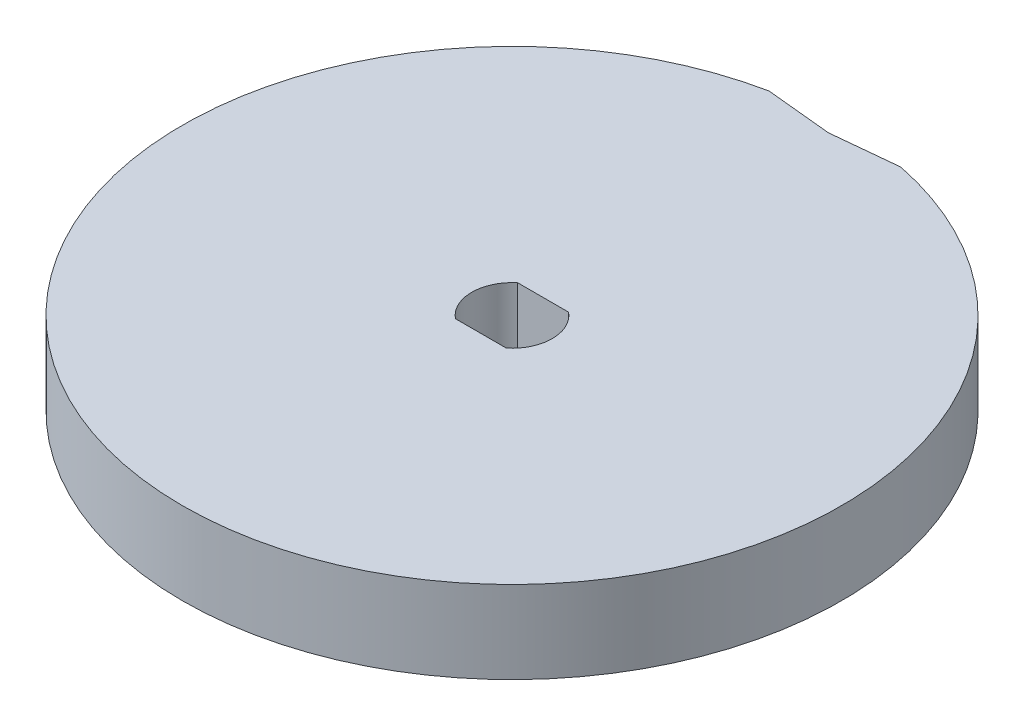
SolidWorks part; units mm, degrees
material "ABS"
ref_plane "Front Plane" through (0, 0, 0) normal (0, 0, 1) x (1, 0, 0)
ref_plane "Top Plane" through (0, 0, 0) normal (0, 1, 0) x (1, 0, 0)
ref_plane "Right Plane" through (0, 0, 0) normal (1, 0, 0) x (0, 0, -1)
ref_axis "x-axis" through (88.99, 0, 0) along (-1, 0, 0)
ref_axis "y-axis" through (0, 0, 55) along (0, 0, -1)
ref_axis "z-axis" through (0, 55, 0) along (0, -1, 0)
sketch "Sketch1" plane through (0, 0, 0) normal (0, 1, 0) x (1, 0, 0)
  circle A0 centre (0, 0) radius 12.7
  dimension "D1" = 25.4
extrude "wheelbase" add sketch "Sketch1" along normal mid plane 3.175
sketch "Sketch3" plane through (0, 1.5875, 0) normal (0, 1, 0) x (1, 0, 0)
  circle A0 centre (0, 0) radius 1.55
  dimension "D1" = 3.1
extrude "circlefit" cut sketch "Sketch3" against normal through all
sketch "Sketch4" plane through (0, 1.5875, 0) normal (0, 1, 0) x (1, 0, 0)
  line L0 (-0.9811, 1.2) -> (0.9811, 1.2)
  circle A0 centre (0, 0) radius 1.55 construction
  arc A1 (-0.9811, 1.2) -> (0.9811, 1.2) centre (0, 0) cw
  dimension "key1" = 1.2
extrude "gm26fit1" add sketch "Sketch4" against normal up to surface (3.175 mm away) up to face at (0, -1.5875, 1.55)
sketch "Sketch5" plane through (0, 1.5875, 0) normal (0, 1, 0) x (1, 0, 0)
  line L0 (-0.9811, -1.2) -> (0.9811, -1.2)
  line L1 (-0.9811, 1.2) -> (0.9811, 1.2) construction
  arc A0 (-0.9811, 1.2) -> (0.9811, 1.2) centre (0, 0) ccw construction
  arc A1 (-0.9811, -1.2) -> (0.9811, -1.2) centre (0, 0) ccw
  dimension "key2" = 2.4
extrude "gm26fit2" add sketch "Sketch5" against normal up to surface (3.175 mm away) up to face at (0, -1.5875, 0.175)
sketch "Sketch6" plane through (0, 1.5875, 0) normal (0, 1, 0) x (1, 0, 0)
  line L0 (-2.54, 12.4434) -> (0, 12.192)
  line L1 (0, 12.192) -> (2.54, 12.4434)
  line L2 (0, 12.192) -> (0, 12.7) construction
  circle A0 centre (0, 0) radius 12.7 construction
  arc A1 (-2.54, 12.4434) -> (2.54, 12.4434) centre (0, 0) cw
  dimension "D1" = 0.508
  dimension "D2" = 5.08
extrude "Cut-Extrude1" cut sketch "Sketch6" against normal through all
equation "\"key2@Sketch5\" = \"key1@Sketch4\"*2"
